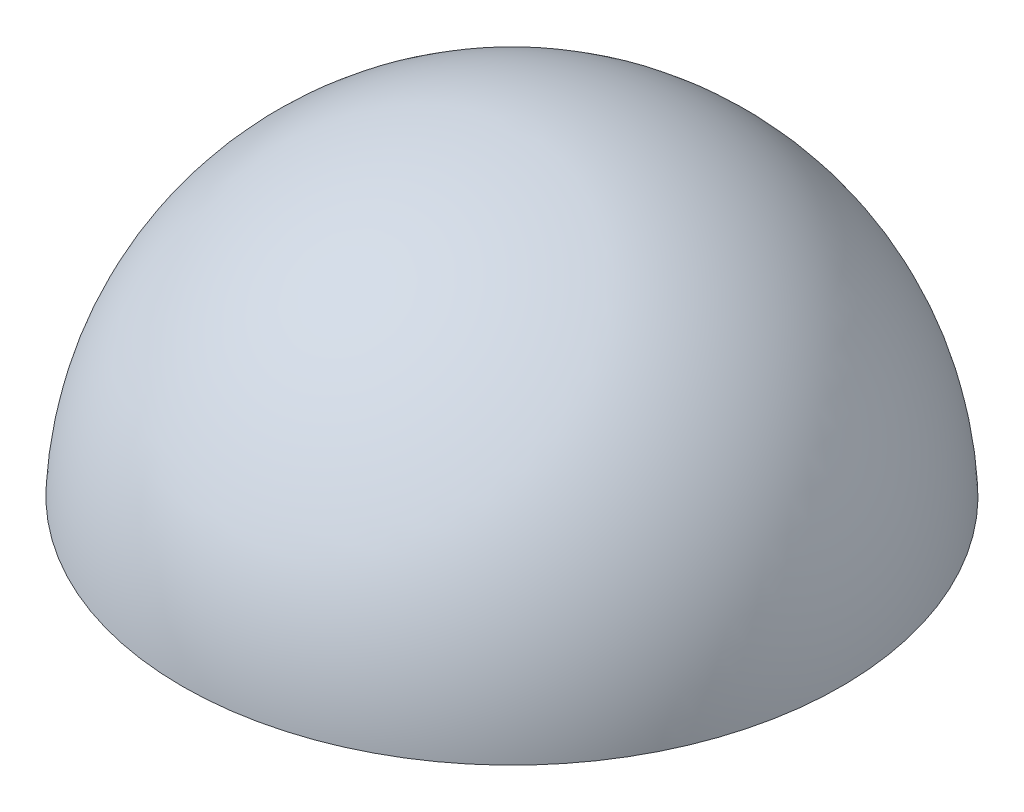
SolidWorks part; units mm, degrees
ref_plane "Front Plane" through (0, 0, 0) normal (0, 0, 1) x (1, 0, 0)
ref_plane "Top Plane" through (0, 0, 0) normal (0, 1, 0) x (1, 0, 0)
ref_plane "Right Plane" through (0, 0, 0) normal (1, 0, 0) x (0, 0, -1)
sketch "Sketch1" plane through (0, 0, 0) normal (0, 1, 0) x (1, 0, 0)
  line L0 (0, -44.45) -> (0, 44.45)
  arc A0 (0, 44.45) -> (0, -44.45) centre (0, 0) ccw
  arc A1 (0, 42.45) -> (0, -42.45) centre (0, 0) ccw
  circle A3 centre (0, 0) radius 44.45 construction
  circle A4 centre (0, 0) radius 42.45 construction
  point P1 (42.45, 0)
  point P6 (42.5077, 12.9959)
  dimension "D1" = 88.9
  dimension "D2" = 2
revolve "Revolve1" add sketch "Sketch1" angle 180 about L0 region at (-43.4561, 0, 0)
sketch "Sketch2" plane through (0, 0, 0) normal (0, 1, 0) x (1, 0, 0)
  circle A0 centre (0, 0) radius 44.45
extrude "Cut-Extrude1" cut sketch "Sketch2" along normal blind 2
sketch "30deg" plane through (0, 0, 0) normal (1, 0, 0) x (0, 0, -1)
  line L0 (0, 0) -> (38.4948, 22.225) construction
  line L1 (0, 0) -> (44.45, 0) construction
  line L7 (0, 0) -> (22.225, 38.4948) construction
  line L8 (0, 0) -> (44.45, 0) construction
  line L10 (0, 0) -> (38.4948, 22.225) construction
  line L25 (0, 0) -> (0, 49000) construction
  dimension "D2" = 3
  dimension "D3" = 30
  dimension "D1" = 44.45
sketch "Sketch4" plane through (0, 0, 0) normal (0, 1, 0) x (1, 0, 0)
  line L0 (0, 0) -> (0, 43.45)
  line L1 (0.5, 44.45) -> (-0.5, 44.45)
  line L2 (-0.5, 43.45) -> (0.5, 43.45)
  line L3 (-0.5, 43.45) -> (-0.5, 44.45)
  line L4 (0.5, 43.45) -> (0.5, 44.45)
  line L5 (0, 0) -> (21.725, 37.6288)
  line L6 (21.292, 37.8788) -> (21.792, 38.7448)
  line L7 (21.292, 37.8788) -> (22.158, 37.3788)
  line L8 (22.158, 37.3788) -> (22.658, 38.2448)
  line L9 (22.658, 38.2448) -> (21.792, 38.7448)
  line L10 (0, 0) -> (37.6288, 21.725)
  line L11 (37.3788, 22.158) -> (38.2448, 22.658)
  line L12 (37.3788, 22.158) -> (37.8788, 21.292)
  line L13 (37.8788, 21.292) -> (38.7448, 21.792)
  line L14 (38.7448, 21.792) -> (38.2448, 22.658)
  line L15 (0, 0) -> (43.45, 0)
  line L16 (43.45, 0.5) -> (44.45, 0.5)
  line L17 (43.45, 0.5) -> (43.45, -0.5)
  line L18 (43.45, -0.5) -> (44.45, -0.5)
  line L19 (44.45, -0.5) -> (44.45, 0.5)
  line L20 (0, 0) -> (37.6288, -21.725)
  line L21 (37.8788, -21.292) -> (38.7448, -21.792)
  line L22 (37.8788, -21.292) -> (37.3788, -22.158)
  line L23 (37.3788, -22.158) -> (38.2448, -22.658)
  line L24 (38.2448, -22.658) -> (38.7448, -21.792)
  line L25 (0, 0) -> (21.725, -37.6288)
  line L26 (22.158, -37.3788) -> (22.658, -38.2448)
  line L27 (22.158, -37.3788) -> (21.292, -37.8788)
  line L28 (21.292, -37.8788) -> (21.792, -38.7448)
  line L29 (21.792, -38.7448) -> (22.658, -38.2448)
  line L30 (0, 0) -> (0, -43.45)
  line L31 (0.5, -43.45) -> (0.5, -44.45)
  line L32 (0.5, -43.45) -> (-0.5, -43.45)
  line L33 (-0.5, -43.45) -> (-0.5, -44.45)
  line L34 (-0.5, -44.45) -> (0.5, -44.45)
  line L35 (0, 0) -> (-21.725, -37.6288)
  line L36 (-21.292, -37.8788) -> (-21.792, -38.7448)
  line L37 (-21.292, -37.8788) -> (-22.158, -37.3788)
  line L38 (-22.158, -37.3788) -> (-22.658, -38.2448)
  line L39 (-22.658, -38.2448) -> (-21.792, -38.7448)
  line L40 (0, 0) -> (-37.6288, -21.725)
  line L41 (-37.3788, -22.158) -> (-38.2448, -22.658)
  line L42 (-37.3788, -22.158) -> (-37.8788, -21.292)
  line L43 (-37.8788, -21.292) -> (-38.7448, -21.792)
  line L44 (-38.7448, -21.792) -> (-38.2448, -22.658)
  line L45 (0, 0) -> (-43.45, 0)
  line L46 (-43.45, -0.5) -> (-44.45, -0.5)
  line L47 (-43.45, -0.5) -> (-43.45, 0.5)
  line L48 (-43.45, 0.5) -> (-44.45, 0.5)
  line L49 (-44.45, 0.5) -> (-44.45, -0.5)
  line L50 (0, 0) -> (-37.6288, 21.725)
  line L51 (-37.8788, 21.292) -> (-38.7448, 21.792)
  line L52 (-37.8788, 21.292) -> (-37.3788, 22.158)
  line L53 (-37.3788, 22.158) -> (-38.2448, 22.658)
  line L54 (-38.2448, 22.658) -> (-38.7448, 21.792)
  line L55 (0, 0) -> (-21.725, 37.6288)
  line L56 (-22.158, 37.3788) -> (-22.658, 38.2448)
  line L57 (-22.158, 37.3788) -> (-21.292, 37.8788)
  line L58 (-21.292, 37.8788) -> (-21.792, 38.7448)
  line L59 (-21.792, 38.7448) -> (-22.658, 38.2448)
  line L60 (0, 0) -> (0, 43.45) construction
  line L61 (0, 0) -> (21.725, 37.6288) construction
  circle A0 centre (0, 0) radius 44.45 construction
  point P7 (0, 44.45)
  point P10 (0, 43.45)
  dimension "D1" = 88.9
  dimension "D2" = 1
  dimension "D3" = 1
  dimension "D5" = 30
  dimension "D4" = 12
ref_plane "Plane1" through (0, 44.45, 0) normal (0, 1, 0) x (1, 0, 0)
sketch "Sketch5" plane through (0, 44.45, 0) normal (0, 1, 0) x (1, 0, 0)
  circle A0 centre (0, 0) radius 0.5
  dimension "D1" = 1
sketch "Sketch6" plane through (0, 0, 0) normal (0, 0, 1) x (1, 0, 0)
  line L0 (44.45, 0) -> (-44.45, 0) construction
  line L1 (-43.45, 0) -> (-44.45, 0) construction
  arc A0 (-44.45, 0) -> (0, 44.45) centre (0, 0) cw
ref_axis "Axis1" through (0, 117.8347, 0) along (0, -1, 0)
sketch "Sketch7" plane through (0, 44.45, 0) normal (0, 1, 0) x (1, 0, 0)
  line L0 (0, 0) -> (0, 88.8986) construction
  line L4 (-0.5, 38.9916) -> (-0.5, 88.8986)
  line L5 (0.5, 38.9916) -> (0.5, 88.8986)
  line L7 (-0.5, 22.7195) -> (-0.5, 37.9915)
  line L9 (0.5, 22.7195) -> (0.5, 37.9915)
  line L10 (0, 0) -> (44.4493, 76.9884) construction
  line L11 (19.0628, 34.0177) -> (44.0163, 77.2384)
  line L12 (19.9288, 33.5177) -> (44.8823, 76.7384)
  line L13 (10.9267, 19.9257) -> (18.5628, 33.1516)
  line L14 (11.7928, 19.4257) -> (19.4288, 32.6516)
  line L17 (0, 0) -> (76.9884, 44.4493) construction
  line L18 (33.5177, 19.9288) -> (76.7384, 44.8823)
  line L19 (34.0177, 19.0628) -> (77.2384, 44.0163)
  line L20 (19.4257, 11.7928) -> (32.6516, 19.4288)
  line L21 (19.9257, 10.9267) -> (33.1516, 18.5628)
  line L24 (0, 0) -> (88.8986, 0) construction
  line L25 (38.9916, 0.5) -> (88.8986, 0.5)
  line L26 (38.9916, -0.5) -> (88.8986, -0.5)
  line L27 (22.7195, 0.5) -> (37.9915, 0.5)
  line L28 (22.7195, -0.5) -> (37.9915, -0.5)
  line L31 (0, 0) -> (76.9884, -44.4493) construction
  line L32 (34.0177, -19.0628) -> (77.2384, -44.0163)
  line L33 (33.5177, -19.9288) -> (76.7384, -44.8823)
  line L34 (19.9257, -10.9267) -> (33.1516, -18.5628)
  line L35 (19.4257, -11.7928) -> (32.6516, -19.4288)
  line L38 (0, 0) -> (44.4493, -76.9884) construction
  line L39 (19.9288, -33.5177) -> (44.8823, -76.7384)
  line L40 (19.0628, -34.0177) -> (44.0163, -77.2384)
  line L41 (11.7928, -19.4257) -> (19.4288, -32.6516)
  line L42 (10.9267, -19.9257) -> (18.5628, -33.1516)
  line L45 (0, 0) -> (0, -88.8986) construction
  line L46 (0.5, -38.9916) -> (0.5, -88.8986)
  line L47 (-0.5, -38.9916) -> (-0.5, -88.8986)
  line L48 (0.5, -22.7195) -> (0.5, -37.9915)
  line L49 (-0.5, -22.7195) -> (-0.5, -37.9915)
  line L52 (0, 0) -> (-44.4493, -76.9884) construction
  line L53 (-19.0628, -34.0177) -> (-44.0163, -77.2384)
  line L54 (-19.9288, -33.5177) -> (-44.8823, -76.7384)
  line L55 (-10.9267, -19.9257) -> (-18.5628, -33.1516)
  line L56 (-11.7928, -19.4257) -> (-19.4288, -32.6516)
  line L59 (0, 0) -> (-76.9884, -44.4493) construction
  line L60 (-33.5177, -19.9288) -> (-76.7384, -44.8823)
  line L61 (-34.0177, -19.0628) -> (-77.2384, -44.0163)
  line L62 (-19.4257, -11.7928) -> (-32.6516, -19.4288)
  line L63 (-19.9257, -10.9267) -> (-33.1516, -18.5628)
  line L66 (0, 0) -> (-88.8986, 0) construction
  line L67 (-38.9916, -0.5) -> (-88.8986, -0.5)
  line L68 (-38.9916, 0.5) -> (-88.8986, 0.5)
  line L69 (-22.7195, -0.5) -> (-37.9915, -0.5)
  line L70 (-22.7195, 0.5) -> (-37.9915, 0.5)
  line L73 (0, 0) -> (-76.9884, 44.4493) construction
  line L74 (-34.0177, 19.0628) -> (-77.2384, 44.0163)
  line L75 (-33.5177, 19.9288) -> (-76.7384, 44.8823)
  line L76 (-19.9257, 10.9267) -> (-33.1516, 18.5628)
  line L77 (-19.4257, 11.7928) -> (-32.6516, 19.4288)
  line L80 (0, 0) -> (-44.4493, 76.9884) construction
  line L81 (-19.9288, 33.5177) -> (-44.8823, 76.7384)
  line L82 (-19.0628, 34.0177) -> (-44.0163, 77.2384)
  line L83 (-11.7928, 19.4257) -> (-19.4288, 32.6516)
  line L84 (-10.9267, 19.9257) -> (-18.5628, 33.1516)
  line L87 (0, 0) -> (0.5, 0) construction
  line L89 (-0.5, 1.866) -> (-0.5, 21.7192)
  line L90 (-0.5, 1.866) -> (-10.4266, 19.0594)
  line L91 (0.5, 1.866) -> (10.4266, 19.0594)
  line L92 (0.5, 1.866) -> (0.5, 21.7192)
  line L93 (1.366, 1.366) -> (18.5594, 11.2926)
  line L94 (1.366, 1.366) -> (11.2926, 18.5594)
  line L95 (1.866, 0.5) -> (21.7192, 0.5)
  line L96 (1.866, 0.5) -> (19.0594, 10.4266)
  line L97 (1.866, -0.5) -> (19.0594, -10.4266)
  line L98 (1.866, -0.5) -> (21.7192, -0.5)
  line L99 (1.366, -1.366) -> (11.2926, -18.5594)
  line L100 (1.366, -1.366) -> (18.5594, -11.2926)
  line L101 (0.5, -1.866) -> (0.5, -21.7192)
  line L102 (0.5, -1.866) -> (10.4266, -19.0594)
  line L103 (-0.5, -1.866) -> (-10.4266, -19.0594)
  line L104 (-0.5, -1.866) -> (-0.5, -21.7192)
  line L105 (-1.366, -1.366) -> (-11.2926, -18.5594)
  line L106 (-1.366, -1.366) -> (-18.5594, -11.2926)
  line L107 (-1.866, -0.5) -> (-21.7192, -0.5)
  line L108 (-1.866, -0.5) -> (-19.0594, -10.4266)
  line L109 (-1.866, 0.5) -> (-19.0594, 10.4266)
  line L110 (-1.866, 0.5) -> (-21.7192, 0.5)
  line L111 (-1.366, 1.366) -> (-11.2926, 18.5594)
  line L112 (-1.366, 1.366) -> (-18.5594, 11.2926)
  circle A0 centre (0, 0) radius 22.225 construction
  circle A1 centre (0, 0) radius 38.4948 construction
  arc A2 (-0.5, 38.9916) -> (-19.0628, 34.0177) centre (0, 0) ccw
  arc A3 (-0.5, 22.7195) -> (-10.9267, 19.9257) centre (0, 0) ccw
  arc A4 (-0.5, 37.9915) -> (-18.5628, 33.1516) centre (0, 0) ccw
  arc A5 (-0.5, 21.7192) -> (-10.4266, 19.0594) centre (0, 0) ccw
  arc A6 (0.5, 88.8986) -> (-0.5, 88.8986) centre (0, 0) ccw
  circle A9 centre (0, 0) radius 88.9 construction
  circle A10 centre (0, 0) radius 38.9948 construction
  circle A11 centre (0, 0) radius 37.9948 construction
  circle A13 centre (0, 0) radius 21.725 construction
  circle A14 centre (0, 0) radius 22.725 construction
  arc A15 (44.8823, 76.7384) -> (44.0163, 77.2384) centre (0, 0) ccw
  arc A16 (77.2384, 44.0163) -> (76.7384, 44.8823) centre (0, 0) ccw
  arc A17 (88.8986, -0.5) -> (88.8986, 0.5) centre (0, 0) ccw
  arc A18 (76.7384, -44.8823) -> (77.2384, -44.0163) centre (0, 0) ccw
  arc A19 (44.0163, -77.2384) -> (44.8823, -76.7384) centre (0, 0) ccw
  arc A20 (-0.5, -88.8986) -> (0.5, -88.8986) centre (0, 0) ccw
  arc A21 (-44.8823, -76.7384) -> (-44.0163, -77.2384) centre (0, 0) ccw
  arc A22 (-77.2384, -44.0163) -> (-76.7384, -44.8823) centre (0, 0) ccw
  arc A23 (-88.8986, 0.5) -> (-88.8986, -0.5) centre (0, 0) ccw
  arc A24 (-76.7384, 44.8823) -> (-77.2384, 44.0163) centre (0, 0) ccw
  arc A25 (-44.0163, 77.2384) -> (-44.8823, 76.7384) centre (0, 0) ccw
  arc A26 (-34.0177, 19.0628) -> (-38.9916, 0.5) centre (0, 0) ccw
  arc A27 (-33.1516, 18.5628) -> (-37.9915, 0.5) centre (0, 0) ccw
  arc A28 (-19.9288, 33.5177) -> (-33.5177, 19.9288) centre (0, 0) ccw
  arc A29 (-19.4288, 32.6516) -> (-32.6516, 19.4288) centre (0, 0) ccw
  arc A30 (19.0628, 34.0177) -> (0.5, 38.9916) centre (0, 0) ccw
  arc A31 (18.5628, 33.1516) -> (0.5, 37.9915) centre (0, 0) ccw
  arc A32 (32.6516, 19.4288) -> (19.4288, 32.6516) centre (0, 0) ccw
  arc A33 (33.5177, 19.9288) -> (19.9288, 33.5177) centre (0, 0) ccw
  arc A34 (37.9915, 0.5) -> (33.1516, 18.5628) centre (0, 0) ccw
  arc A35 (38.9916, 0.5) -> (34.0177, 19.0628) centre (0, 0) ccw
  arc A36 (33.1516, -18.5628) -> (37.9915, -0.5) centre (0, 0) ccw
  arc A37 (34.0177, -19.0628) -> (38.9916, -0.5) centre (0, 0) ccw
  arc A38 (19.4288, -32.6516) -> (32.6516, -19.4288) centre (0, 0) ccw
  arc A39 (19.9288, -33.5177) -> (33.5177, -19.9288) centre (0, 0) ccw
  arc A40 (0.5, -37.9915) -> (18.5628, -33.1516) centre (0, 0) ccw
  arc A41 (0.5, -38.9916) -> (19.0628, -34.0177) centre (0, 0) ccw
  arc A42 (-18.5628, -33.1516) -> (-0.5, -37.9915) centre (0, 0) ccw
  arc A43 (-19.0628, -34.0177) -> (-0.5, -38.9916) centre (0, 0) ccw
  arc A44 (-33.5177, -19.9288) -> (-19.9288, -33.5177) centre (0, 0) ccw
  arc A45 (-32.6516, -19.4288) -> (-19.4288, -32.6516) centre (0, 0) ccw
  arc A46 (-38.9916, -0.5) -> (-34.0177, -19.0628) centre (0, 0) ccw
  arc A47 (-37.9915, -0.5) -> (-33.1516, -18.5628) centre (0, 0) ccw
  arc A48 (-11.7928, 19.4257) -> (-19.4257, 11.7928) centre (0, 0) ccw
  arc A49 (-11.2926, 18.5594) -> (-18.5594, 11.2926) centre (0, 0) ccw
  arc A50 (-19.9257, 10.9267) -> (-22.7195, 0.5) centre (0, 0) ccw
  arc A51 (-19.0594, 10.4266) -> (-21.7192, 0.5) centre (0, 0) ccw
  arc A52 (-21.7192, -0.5) -> (-19.0594, -10.4266) centre (0, 0) ccw
  arc A53 (-22.7195, -0.5) -> (-19.9257, -10.9267) centre (0, 0) ccw
  arc A54 (10.4266, 19.0594) -> (0.5, 21.7192) centre (0, 0) ccw
  arc A55 (10.9267, 19.9257) -> (0.5, 22.7195) centre (0, 0) ccw
  arc A56 (18.5594, 11.2926) -> (11.2926, 18.5594) centre (0, 0) ccw
  arc A57 (19.4257, 11.7928) -> (11.7928, 19.4257) centre (0, 0) ccw
  arc A58 (21.7192, 0.5) -> (19.0594, 10.4266) centre (0, 0) ccw
  arc A59 (22.7195, 0.5) -> (19.9257, 10.9267) centre (0, 0) ccw
  arc A60 (19.9257, -10.9267) -> (22.7195, -0.5) centre (0, 0) ccw
  arc A61 (19.0594, -10.4266) -> (21.7192, -0.5) centre (0, 0) ccw
  arc A62 (11.2926, -18.5594) -> (18.5594, -11.2926) centre (0, 0) ccw
  arc A63 (11.7928, -19.4257) -> (19.4257, -11.7928) centre (0, 0) ccw
  arc A64 (0.5, -22.7195) -> (10.9267, -19.9257) centre (0, 0) ccw
  arc A65 (0.5, -21.7192) -> (10.4266, -19.0594) centre (0, 0) ccw
  arc A66 (-10.4266, -19.0594) -> (-0.5, -21.7192) centre (0, 0) ccw
  arc A67 (-10.9267, -19.9257) -> (-0.5, -22.7195) centre (0, 0) ccw
  arc A68 (-19.4257, -11.7928) -> (-11.7928, -19.4257) centre (0, 0) ccw
  arc A69 (-18.5594, -11.2926) -> (-11.2926, -18.5594) centre (0, 0) ccw
  point P11 (21.725, 0)
  point P13 (22.725, 0)
  point P17 (0.5, 0)
  point P19 (-0.5, 0)
  point P27 (38.9948, 0)
  point P30 (37.9948, 0)
  point P114 (-1.366, 1.366)
  dimension "D5" = 177.8
  dimension "D1" = 0.5
  dimension "D2" = 0.5
  dimension "D6" = 12
sketch "Sketch9" plane through (0, 44.45, 0) normal (0, 1, 0) x (1, 0, 0)
  line L0 (0, 0) -> (0, -88.9)
  circle A0 centre (0, 0) radius 22.225
  circle A1 centre (0, 0) radius 38.4948
  circle A2 centre (0, 0) radius 88.9
  circle A3 centre (0, 0) radius 38.4948 construction
  circle A4 centre (0, 0) radius 22.225 construction
  dimension "D1" = 177.8
sketch "Sketch10" plane through (0, 44.45, 0) normal (0, 1, 0) x (1, 0, 0)
  line L0 (88.9, 0) -> (-88.9, 0) construction
  line L1 (0, 88.9) -> (0, -88.9) construction
  line L2 (-29.64, 88.9) -> (-29.64, -88.9) construction
  line L3 (-59.28, 88.9) -> (-59.28, -88.9) construction
  line L4 (-88.92, 88.9) -> (-88.92, -88.9) construction
  line L5 (29.64, 88.9) -> (29.64, -88.9) construction
  line L6 (59.28, 88.9) -> (59.28, -88.9) construction
  line L7 (88.92, 88.9) -> (88.92, -88.9) construction
  line L8 (-89.42, 88.9) -> (-89.42, -88.9)
  line L9 (-59.78, 88.9) -> (-59.78, 0.5)
  line L10 (-30.14, 88.9) -> (-30.14, 0.5)
  line L11 (-0.5, 88.9) -> (-0.5, 0.5)
  line L12 (29.14, 88.9) -> (29.14, 0.5)
  line L13 (58.78, 88.9) -> (58.78, 0.5)
  line L14 (88.42, 88.9) -> (88.42, 0.5)
  line L15 (-88.42, 88.9) -> (-88.42, 0.5)
  line L16 (-58.78, 88.9) -> (-58.78, 0.5)
  line L17 (-29.14, 88.9) -> (-29.14, 0.5)
  line L18 (0.5, 88.9) -> (0.5, 0.5)
  line L19 (30.14, 88.9) -> (30.14, 0.5)
  line L20 (59.78, 88.9) -> (59.78, 0.5)
  line L21 (89.42, 88.9) -> (89.42, -88.9)
  line L22 (88.42, 0.5) -> (59.78, 0.5)
  line L23 (88.42, -0.5) -> (59.78, -0.5)
  line L24 (-88.42, -0.5) -> (-88.42, -88.9)
  line L25 (88.9, 0.5) -> (-88.9, 0.5) construction
  line L26 (88.9, -0.5) -> (-88.9, -0.5) construction
  line L27 (-59.78, 0.5) -> (-88.42, 0.5)
  line L28 (-88.42, 88.9) -> (-88.42, -88.9) construction
  line L29 (-59.78, -0.5) -> (-88.42, -0.5)
  line L30 (-59.78, -0.5) -> (-59.78, -88.9)
  line L31 (-58.78, -0.5) -> (-58.78, -88.9)
  line L32 (-59.78, 88.9) -> (-59.78, -88.9) construction
  line L33 (-30.14, -0.5) -> (-30.14, -88.9)
  line L34 (-58.78, 88.9) -> (-58.78, -88.9) construction
  line L35 (-30.14, 88.9) -> (-30.14, -88.9) construction
  line L36 (-29.14, -0.5) -> (-29.14, -88.9)
  line L37 (-29.14, 88.9) -> (-29.14, -88.9) construction
  line L38 (-0.5, -0.5) -> (-0.5, -88.9)
  line L39 (-0.5, 88.9) -> (-0.5, -88.9) construction
  line L40 (0.5, -0.5) -> (0.5, -88.9)
  line L41 (0.5, 88.9) -> (0.5, -88.9) construction
  line L42 (29.14, -0.5) -> (29.14, -88.9)
  line L43 (29.14, 88.9) -> (29.14, -88.9) construction
  line L44 (30.14, -0.5) -> (30.14, -88.9)
  line L45 (30.14, 88.9) -> (30.14, -88.9) construction
  line L46 (58.78, -0.5) -> (58.78, -88.9)
  line L47 (58.78, 88.9) -> (58.78, -88.9) construction
  line L48 (59.78, -0.5) -> (59.78, -88.9)
  line L49 (59.78, 88.9) -> (59.78, -88.9) construction
  line L50 (88.42, -0.5) -> (88.42, -88.9)
  line L51 (88.42, 88.9) -> (88.42, -88.9) construction
  line L52 (58.78, 0.5) -> (30.14, 0.5)
  line L53 (58.78, -0.5) -> (30.14, -0.5)
  line L54 (-30.14, 0.5) -> (-58.78, 0.5)
  line L55 (-30.14, -0.5) -> (-58.78, -0.5)
  line L56 (-0.5, 0.5) -> (-29.14, 0.5)
  line L57 (-0.5, -0.5) -> (-29.14, -0.5)
  line L58 (29.14, 0.5) -> (0.5, 0.5)
  line L59 (29.14, -0.5) -> (0.5, -0.5)
  arc A0 (-89.42, 88.9) -> (-88.42, 88.9) centre (-88.92, 88.9) cw
  arc A1 (-89.42, -88.9) -> (-88.42, -88.9) centre (-88.92, -88.9) ccw
  arc A2 (-59.78, 88.9) -> (-58.78, 88.9) centre (-59.28, 88.9) cw
  arc A3 (-59.78, -88.9) -> (-58.78, -88.9) centre (-59.28, -88.9) ccw
  arc A4 (-30.14, 88.9) -> (-29.14, 88.9) centre (-29.64, 88.9) cw
  arc A5 (-30.14, -88.9) -> (-29.14, -88.9) centre (-29.64, -88.9) ccw
  arc A6 (-0.5, 88.9) -> (0.5, 88.9) centre (0, 88.9) cw
  arc A7 (-0.5, -88.9) -> (0.5, -88.9) centre (0, -88.9) ccw
  arc A8 (29.14, 88.9) -> (30.14, 88.9) centre (29.64, 88.9) cw
  arc A9 (29.14, -88.9) -> (30.14, -88.9) centre (29.64, -88.9) ccw
  arc A10 (58.78, 88.9) -> (59.78, 88.9) centre (59.28, 88.9) cw
  arc A11 (58.78, -88.9) -> (59.78, -88.9) centre (59.28, -88.9) ccw
  arc A12 (88.42, 88.9) -> (89.42, 88.9) centre (88.92, 88.9) cw
  arc A13 (88.42, -88.9) -> (89.42, -88.9) centre (88.92, -88.9) ccw
  arc A15 (-88.9, 0.5) -> (-88.92, 0.4996) centre (-88.9, 0) ccw
  arc A16 (-88.92, -0.4996) -> (-88.9, -0.5) centre (-88.9, 0) ccw
  point P4 (0, 0)
  point P8 (0, 0)
  dimension "D1" = 177.8
  dimension "D3" = 0.5
  dimension "D4" = 0.5
  dimension "D5" = 0.5
  dimension "D6" = 0.5
  dimension "D2" = 4
sketch "Sketch13" plane through (0, 44.45, 0) normal (0, 1, 0) x (1, 0, 0)
  line L0 (0, -11.5265) -> (0, 11.5265) construction
  line L1 (-11.5265, 0) -> (11.5265, 0) construction
  line L2 (-11.5265, -0.5) -> (-0.5, -0.5)
  line L3 (-18.1069, 3.2902) -> (-11.5265, 3.2902) construction
  line L4 (-18.1069, 3.2902) -> (-18.1069, -3.2902) construction
  line L5 (-18.1069, -3.2902) -> (-11.5265, -3.2902) construction
  line L6 (-11.5265, 3.2902) -> (-11.5265, -3.2902) construction
  line L7 (-3.2902, 18.1069) -> (3.2902, 18.1069) construction
  line L8 (-3.2902, 18.1069) -> (-3.2902, 11.5265) construction
  line L9 (-3.2902, 11.5265) -> (3.2902, 11.5265) construction
  line L10 (3.2902, 18.1069) -> (3.2902, 11.5265) construction
  line L11 (0.5, -11.5265) -> (0.5, -0.5)
  line L12 (-11.5265, 0.5) -> (-0.5, 0.5)
  line L13 (-0.5, -11.5265) -> (-0.5, -0.5)
  line L14 (-0.5, 0.5) -> (-0.5, 11.5265)
  line L15 (0.5, 0.5) -> (0.5, 11.5265)
  line L16 (-0.5, -11.5265) -> (-0.5, 11.5265) construction
  line L17 (0.5, 0.5) -> (11.5265, 0.5)
  line L18 (0.5, -11.5265) -> (0.5, 11.5265) construction
  line L19 (0.5, -0.5) -> (11.5265, -0.5)
  line L20 (-11.5265, 0.5) -> (11.5265, 0.5) construction
  line L21 (-11.5265, 0.5) -> (-11.5265, -0.5)
  line L22 (-11.5265, -0.5) -> (11.5265, -0.5) construction
  line L23 (11.5265, 0.5) -> (11.5265, -0.5)
  line L24 (-0.5, -11.5265) -> (0.5, -11.5265)
  line L25 (-0.5, 11.5265) -> (0.5, 11.5265)
  line L26 (18.1035, -0.5) -> (29.13, -0.5)
  line L27 (30.13, -11.5265) -> (30.13, -0.5)
  line L28 (18.1035, 0.5) -> (29.13, 0.5)
  line L29 (29.13, -11.5265) -> (29.13, -0.5)
  line L30 (29.13, 0.5) -> (29.13, 11.5265)
  line L31 (30.13, 0.5) -> (30.13, 11.5265)
  line L32 (30.13, 0.5) -> (41.1565, 0.5)
  line L33 (30.13, -0.5) -> (41.1565, -0.5)
  line L34 (18.1035, 0.5) -> (18.1035, -0.5)
  line L35 (41.1565, 0.5) -> (41.1565, -0.5)
  line L36 (29.13, -11.5265) -> (30.13, -11.5265)
  line L37 (29.13, 11.5265) -> (30.13, 11.5265)
  line L38 (29.63, -11.5265) -> (29.63, 11.5265) construction
  line L39 (18.1035, 0) -> (41.1565, 0) construction
  line L40 (11.5231, 3.2902) -> (18.1035, 3.2902) construction
  line L41 (11.5231, 3.2902) -> (11.5231, -3.2902) construction
  line L42 (11.5231, -3.2902) -> (18.1035, -3.2902) construction
  line L43 (18.1035, 3.2902) -> (18.1035, -3.2902) construction
  line L44 (26.3398, 18.1069) -> (32.9202, 18.1069) construction
  line L45 (26.3398, 18.1069) -> (26.3398, 11.5265) construction
  line L46 (26.3398, 11.5265) -> (32.9202, 11.5265) construction
  line L47 (32.9202, 18.1069) -> (32.9202, 11.5265) construction
  line L48 (47.7335, -0.5) -> (58.76, -0.5)
  line L49 (59.76, -11.5265) -> (59.76, -0.5)
  line L50 (47.7335, 0.5) -> (58.76, 0.5)
  line L51 (58.76, -11.5265) -> (58.76, -0.5)
  line L52 (58.76, 0.5) -> (58.76, 11.5265)
  line L53 (59.76, 0.5) -> (59.76, 11.5265)
  line L54 (59.76, 0.5) -> (70.7865, 0.5)
  line L55 (59.76, -0.5) -> (70.7865, -0.5)
  line L56 (47.7335, 0.5) -> (47.7335, -0.5)
  line L57 (70.7865, 0.5) -> (70.7865, -0.5)
  line L58 (58.76, -11.5265) -> (59.76, -11.5265)
  line L59 (58.76, 11.5265) -> (59.76, 11.5265)
  line L60 (59.26, -11.5265) -> (59.26, 11.5265) construction
  line L61 (47.7335, 0) -> (70.7865, 0) construction
  line L62 (41.1531, 3.2902) -> (47.7335, 3.2902) construction
  line L63 (41.1531, 3.2902) -> (41.1531, -3.2902) construction
  line L64 (41.1531, -3.2902) -> (47.7335, -3.2902) construction
  line L65 (47.7335, 3.2902) -> (47.7335, -3.2902) construction
  line L66 (55.9698, 18.1069) -> (62.5502, 18.1069) construction
  line L67 (55.9698, 18.1069) -> (55.9698, 11.5265) construction
  line L68 (55.9698, 11.5265) -> (62.5502, 11.5265) construction
  line L69 (62.5502, 18.1069) -> (62.5502, 11.5265) construction
  line L70 (-11.5265, 29.13) -> (-0.5, 29.13)
  line L71 (0.5, 18.1035) -> (0.5, 29.13)
  line L72 (-11.5265, 30.13) -> (-0.5, 30.13)
  line L73 (-0.5, 18.1035) -> (-0.5, 29.13)
  line L74 (-0.5, 30.13) -> (-0.5, 41.1565)
  line L75 (0.5, 30.13) -> (0.5, 41.1565)
  line L76 (0.5, 30.13) -> (11.5265, 30.13)
  line L77 (0.5, 29.13) -> (11.5265, 29.13)
  line L78 (-11.5265, 30.13) -> (-11.5265, 29.13)
  line L79 (11.5265, 30.13) -> (11.5265, 29.13)
  line L80 (-0.5, 18.1035) -> (0.5, 18.1035)
  line L81 (-0.5, 41.1565) -> (0.5, 41.1565)
  line L82 (18.1035, 29.13) -> (29.13, 29.13)
  line L83 (30.13, 18.1035) -> (30.13, 29.13)
  line L84 (18.1035, 30.13) -> (29.13, 30.13)
  line L85 (29.13, 18.1035) -> (29.13, 29.13)
  line L86 (29.13, 30.13) -> (29.13, 41.1565)
  line L87 (30.13, 30.13) -> (30.13, 41.1565)
  line L88 (30.13, 30.13) -> (41.1565, 30.13)
  line L89 (30.13, 29.13) -> (41.1565, 29.13)
  line L90 (18.1035, 30.13) -> (18.1035, 29.13)
  line L91 (41.1565, 30.13) -> (41.1565, 29.13)
  line L92 (29.13, 18.1035) -> (30.13, 18.1035)
  line L93 (29.13, 41.1565) -> (30.13, 41.1565)
  line L94 (47.7335, 29.13) -> (58.76, 29.13)
  line L95 (59.76, 18.1035) -> (59.76, 29.13)
  line L96 (47.7335, 30.13) -> (58.76, 30.13)
  line L97 (58.76, 18.1035) -> (58.76, 29.13)
  line L98 (58.76, 30.13) -> (58.76, 41.1565)
  line L99 (59.76, 30.13) -> (59.76, 41.1565)
  line L100 (59.76, 30.13) -> (70.7865, 30.13)
  line L101 (59.76, 29.13) -> (70.7865, 29.13)
  line L102 (47.7335, 30.13) -> (47.7335, 29.13)
  line L103 (70.7865, 30.13) -> (70.7865, 29.13)
  line L104 (58.76, 18.1035) -> (59.76, 18.1035)
  line L105 (58.76, 41.1565) -> (59.76, 41.1565)
  line L106 (0, 18.1035) -> (0, 41.1565) construction
  line L107 (-11.5265, 29.63) -> (11.5265, 29.63) construction
  line L108 (-18.1069, 32.9202) -> (-11.5265, 32.9202) construction
  line L109 (-18.1069, 32.9202) -> (-18.1069, 26.3398) construction
  line L110 (-18.1069, 26.3398) -> (-11.5265, 26.3398) construction
  line L111 (-11.5265, 32.9202) -> (-11.5265, 26.3398) construction
  line L112 (-3.2902, 47.7369) -> (3.2902, 47.7369) construction
  line L113 (-3.2902, 47.7369) -> (-3.2902, 41.1565) construction
  line L114 (-3.2902, 41.1565) -> (3.2902, 41.1565) construction
  line L115 (3.2902, 47.7369) -> (3.2902, 41.1565) construction
  line L116 (29.63, 18.1035) -> (29.63, 41.1565) construction
  line L117 (18.1035, 29.63) -> (41.1565, 29.63) construction
  line L118 (11.5231, 32.9202) -> (18.1035, 32.9202) construction
  line L119 (11.5231, 32.9202) -> (11.5231, 26.3398) construction
  line L120 (11.5231, 26.3398) -> (18.1035, 26.3398) construction
  line L121 (18.1035, 32.9202) -> (18.1035, 26.3398) construction
  line L122 (26.3398, 47.7369) -> (32.9202, 47.7369) construction
  line L123 (26.3398, 47.7369) -> (26.3398, 41.1565) construction
  line L124 (26.3398, 41.1565) -> (32.9202, 41.1565) construction
  line L125 (32.9202, 47.7369) -> (32.9202, 41.1565) construction
  line L126 (59.26, 18.1035) -> (59.26, 41.1565) construction
  line L127 (47.7335, 29.63) -> (70.7865, 29.63) construction
  line L128 (41.1531, 32.9202) -> (47.7335, 32.9202) construction
  line L129 (41.1531, 32.9202) -> (41.1531, 26.3398) construction
  line L130 (41.1531, 26.3398) -> (47.7335, 26.3398) construction
  line L131 (47.7335, 32.9202) -> (47.7335, 26.3398) construction
  line L132 (55.9698, 47.7369) -> (62.5502, 47.7369) construction
  line L133 (55.9698, 47.7369) -> (55.9698, 41.1565) construction
  line L134 (55.9698, 41.1565) -> (62.5502, 41.1565) construction
  line L135 (62.5502, 47.7369) -> (62.5502, 41.1565) construction
  line L136 (-11.5265, 58.76) -> (-0.5, 58.76)
  line L137 (0.5, 47.7335) -> (0.5, 58.76)
  line L138 (-11.5265, 59.76) -> (-0.5, 59.76)
  line L139 (-0.5, 47.7335) -> (-0.5, 58.76)
  line L140 (-0.5, 59.76) -> (-0.5, 70.7865)
  line L141 (0.5, 59.76) -> (0.5, 70.7865)
  line L142 (0.5, 59.76) -> (11.5265, 59.76)
  line L143 (0.5, 58.76) -> (11.5265, 58.76)
  line L144 (-11.5265, 59.76) -> (-11.5265, 58.76)
  line L145 (11.5265, 59.76) -> (11.5265, 58.76)
  line L146 (-0.5, 47.7335) -> (0.5, 47.7335)
  line L147 (-0.5, 70.7865) -> (0.5, 70.7865)
  line L148 (18.1035, 58.76) -> (29.13, 58.76)
  line L149 (30.13, 47.7335) -> (30.13, 58.76)
  line L150 (18.1035, 59.76) -> (29.13, 59.76)
  line L151 (29.13, 47.7335) -> (29.13, 58.76)
  line L152 (29.13, 59.76) -> (29.13, 70.7865)
  line L153 (30.13, 59.76) -> (30.13, 70.7865)
  line L154 (30.13, 59.76) -> (41.1565, 59.76)
  line L155 (30.13, 58.76) -> (41.1565, 58.76)
  line L156 (18.1035, 59.76) -> (18.1035, 58.76)
  line L157 (41.1565, 59.76) -> (41.1565, 58.76)
  line L158 (29.13, 47.7335) -> (30.13, 47.7335)
  line L159 (29.13, 70.7865) -> (30.13, 70.7865)
  line L160 (47.7335, 58.76) -> (58.76, 58.76)
  line L161 (59.76, 47.7335) -> (59.76, 58.76)
  line L162 (47.7335, 59.76) -> (58.76, 59.76)
  line L163 (58.76, 47.7335) -> (58.76, 58.76)
  line L164 (58.76, 59.76) -> (58.76, 70.7865)
  line L165 (59.76, 59.76) -> (59.76, 70.7865)
  line L166 (59.76, 59.76) -> (70.7865, 59.76)
  line L167 (59.76, 58.76) -> (70.7865, 58.76)
  line L168 (47.7335, 59.76) -> (47.7335, 58.76)
  line L169 (70.7865, 59.76) -> (70.7865, 58.76)
  line L170 (58.76, 47.7335) -> (59.76, 47.7335)
  line L171 (58.76, 70.7865) -> (59.76, 70.7865)
  line L172 (0, 47.7335) -> (0, 70.7865) construction
  line L173 (-11.5265, 59.26) -> (11.5265, 59.26) construction
  line L174 (-18.1069, 62.5502) -> (-11.5265, 62.5502) construction
  line L175 (-18.1069, 62.5502) -> (-18.1069, 55.9698) construction
  line L176 (-18.1069, 55.9698) -> (-11.5265, 55.9698) construction
  line L177 (-11.5265, 62.5502) -> (-11.5265, 55.9698) construction
  line L178 (-3.2902, 77.3669) -> (3.2902, 77.3669) construction
  line L179 (-3.2902, 77.3669) -> (-3.2902, 70.7865) construction
  line L180 (-3.2902, 70.7865) -> (3.2902, 70.7865) construction
  line L181 (3.2902, 77.3669) -> (3.2902, 70.7865) construction
  line L182 (29.63, 47.7335) -> (29.63, 70.7865) construction
  line L183 (18.1035, 59.26) -> (41.1565, 59.26) construction
  line L184 (11.5231, 62.5502) -> (18.1035, 62.5502) construction
  line L185 (11.5231, 62.5502) -> (11.5231, 55.9698) construction
  line L186 (11.5231, 55.9698) -> (18.1035, 55.9698) construction
  line L187 (18.1035, 62.5502) -> (18.1035, 55.9698) construction
  line L188 (26.3398, 77.3669) -> (32.9202, 77.3669) construction
  line L189 (26.3398, 77.3669) -> (26.3398, 70.7865) construction
  line L190 (26.3398, 70.7865) -> (32.9202, 70.7865) construction
  line L191 (32.9202, 77.3669) -> (32.9202, 70.7865) construction
  line L192 (59.26, 47.7335) -> (59.26, 70.7865) construction
  line L193 (47.7335, 59.26) -> (70.7865, 59.26) construction
  line L194 (41.1531, 62.5502) -> (47.7335, 62.5502) construction
  line L195 (41.1531, 62.5502) -> (41.1531, 55.9698) construction
  line L196 (41.1531, 55.9698) -> (47.7335, 55.9698) construction
  line L197 (47.7335, 62.5502) -> (47.7335, 55.9698) construction
  line L198 (55.9698, 77.3669) -> (62.5502, 77.3669) construction
  line L199 (55.9698, 77.3669) -> (55.9698, 70.7865) construction
  line L200 (55.9698, 70.7865) -> (62.5502, 70.7865) construction
  line L201 (62.5502, 77.3669) -> (62.5502, 70.7865) construction
  circle A0 centre (0, 0) radius 88.9 construction
  point P4 (0, 0)
  point P8 (0, 0)
  point P12 (-11.5265, 0)
  point P35 (29.63, 0)
  point P38 (29.63, 0)
  point P61 (59.26, 0)
  point P64 (59.26, 0)
  point P86 (0, 29.63)
  point P89 (0, 29.63)
  point P112 (29.63, 29.63)
  point P115 (29.63, 29.63)
  point P138 (59.26, 29.63)
  point P141 (59.26, 29.63)
  point P164 (0, 59.26)
  point P167 (0, 59.26)
  point P190 (29.63, 59.26)
  point P193 (29.63, 59.26)
  point P216 (59.26, 59.26)
  point P219 (59.26, 59.26)
  dimension "D1" = 177.8
  dimension "D2" = 29.6333
  dimension "D3" = 0.5
  dimension "D4" = 0.5
  dimension "D5" = 3
  dimension "D6" = 3
sketch "Sketch14" plane through (0, 44.45, 0) normal (0, 1, 0) x (1, 0, 0)
  line L0 (94.2855, -48.3857) -> (94.2855, -57.7964) construction
  line L13 (98.9909, -53.0911) -> (89.5802, -53.0911) construction
  line L14 (98.9909, -52.5911) -> (94.7855, -52.5911)
  line L15 (84.1742, -55.7941) -> (89.5802, -55.7941) construction
  line L16 (84.1742, -55.7941) -> (84.1742, -50.3881) construction
  line L17 (84.1742, -50.3881) -> (89.5802, -50.3881) construction
  line L18 (89.5802, -55.7941) -> (89.5802, -50.3881) construction
  line L19 (98.9909, -37.7711) -> (94.7855, -37.7711)
  line L20 (93.7855, -33.5657) -> (93.7855, -37.7711)
  line L21 (91.5825, -42.9798) -> (96.9885, -42.9798) construction
  line L22 (91.5825, -42.9798) -> (91.5825, -48.3857) construction
  line L23 (91.5825, -48.3857) -> (96.9885, -48.3857) construction
  line L24 (96.9885, -42.9798) -> (96.9885, -48.3857) construction
  line L25 (98.9909, -38.7711) -> (94.7855, -38.7711)
  line L26 (94.7855, -33.5657) -> (94.7855, -37.7711)
  line L27 (93.7855, -48.3857) -> (93.7855, -52.5911)
  line L28 (98.9909, -53.5911) -> (94.7855, -53.5911)
  line L29 (94.7855, -48.3857) -> (94.7855, -52.5911)
  line L30 (98.9909, -52.5911) -> (98.9909, -53.5911)
  line L31 (89.5802, -52.5911) -> (89.5802, -53.5911)
  line L32 (93.7855, -48.3857) -> (94.7855, -48.3857)
  line L33 (93.7855, -57.7964) -> (94.7855, -57.7964)
  line L34 (93.7855, -53.5911) -> (93.7855, -57.7964)
  line L35 (93.7855, -53.5911) -> (89.5802, -53.5911)
  line L36 (93.7855, -48.3857) -> (93.7855, -57.7964) construction
  line L37 (94.7855, -53.5911) -> (94.7855, -57.7964)
  line L38 (98.9909, -53.5911) -> (89.5802, -53.5911) construction
  line L39 (93.7855, -52.5911) -> (89.5802, -52.5911)
  line L40 (94.7855, -48.3857) -> (94.7855, -57.7964) construction
  line L41 (98.9909, -37.7711) -> (98.9909, -38.7711)
  line L42 (98.9909, -52.5911) -> (89.5802, -52.5911) construction
  line L43 (89.5802, -37.7711) -> (89.5802, -38.7711)
  line L44 (93.7855, -33.5657) -> (94.7855, -33.5657)
  line L45 (93.7855, -42.9764) -> (94.7855, -42.9764)
  line L46 (93.7855, -38.7711) -> (93.7855, -42.9764)
  line L47 (93.7855, -38.7711) -> (89.5802, -38.7711)
  line L48 (94.7855, -38.7711) -> (94.7855, -42.9764)
  line L49 (93.7855, -37.7711) -> (89.5802, -37.7711)
  line L50 (94.2855, -33.5657) -> (94.2855, -42.9764) construction
  line L51 (98.9909, -38.2711) -> (89.5802, -38.2711) construction
  line L52 (84.1742, -40.9741) -> (89.5802, -40.9741) construction
  line L53 (84.1742, -40.9741) -> (84.1742, -35.5681) construction
  line L54 (84.1742, -35.5681) -> (89.5802, -35.5681) construction
  line L55 (89.5802, -40.9741) -> (89.5802, -35.5681) construction
  line L56 (91.5825, -28.1598) -> (96.9885, -28.1598) construction
  line L57 (91.5825, -28.1598) -> (91.5825, -33.5657) construction
  line L58 (91.5825, -33.5657) -> (96.9885, -33.5657) construction
  line L59 (96.9885, -28.1598) -> (96.9885, -33.5657) construction
  line L60 (98.9909, -22.9511) -> (94.7855, -22.9511)
  line L61 (93.7855, -18.7457) -> (93.7855, -22.9511)
  line L62 (98.9909, -23.9511) -> (94.7855, -23.9511)
  line L63 (94.7855, -18.7457) -> (94.7855, -22.9511)
  line L64 (98.9909, -22.9511) -> (98.9909, -23.9511)
  line L65 (89.5802, -22.9511) -> (89.5802, -23.9511)
  line L66 (93.7855, -18.7457) -> (94.7855, -18.7457)
  line L67 (93.7855, -28.1564) -> (94.7855, -28.1564)
  line L68 (93.7855, -23.9511) -> (93.7855, -28.1564)
  line L69 (93.7855, -23.9511) -> (89.5802, -23.9511)
  line L70 (94.7855, -23.9511) -> (94.7855, -28.1564)
  line L71 (93.7855, -22.9511) -> (89.5802, -22.9511)
  line L72 (94.2855, -18.7457) -> (94.2855, -28.1564) construction
  line L73 (98.9909, -23.4511) -> (89.5802, -23.4511) construction
  line L74 (84.1742, -26.1541) -> (89.5802, -26.1541) construction
  line L75 (84.1742, -26.1541) -> (84.1742, -20.7481) construction
  line L76 (84.1742, -20.7481) -> (89.5802, -20.7481) construction
  line L77 (89.5802, -26.1541) -> (89.5802, -20.7481) construction
  line L78 (91.5825, -13.3398) -> (96.9885, -13.3398) construction
  line L79 (91.5825, -13.3398) -> (91.5825, -18.7457) construction
  line L80 (91.5825, -18.7457) -> (96.9885, -18.7457) construction
  line L81 (96.9885, -13.3398) -> (96.9885, -18.7457) construction
  line L82 (98.9909, -8.1311) -> (94.7855, -8.1311)
  line L83 (93.7855, -3.9257) -> (93.7855, -8.1311)
  line L84 (98.9909, -9.1311) -> (94.7855, -9.1311)
  line L85 (94.7855, -3.9257) -> (94.7855, -8.1311)
  line L86 (98.9909, -8.1311) -> (98.9909, -9.1311)
  line L87 (89.5802, -8.1311) -> (89.5802, -9.1311)
  line L88 (93.7855, -3.9257) -> (94.7855, -3.9257)
  line L89 (93.7855, -13.3364) -> (94.7855, -13.3364)
  line L90 (93.7855, -9.1311) -> (93.7855, -13.3364)
  line L91 (93.7855, -9.1311) -> (89.5802, -9.1311)
  line L92 (94.7855, -9.1311) -> (94.7855, -13.3364)
  line L93 (93.7855, -8.1311) -> (89.5802, -8.1311)
  line L94 (94.2855, -3.9257) -> (94.2855, -13.3364) construction
  line L95 (98.9909, -8.6311) -> (89.5802, -8.6311) construction
  line L96 (84.1742, -11.3341) -> (89.5802, -11.3341) construction
  line L97 (84.1742, -11.3341) -> (84.1742, -5.9281) construction
  line L98 (84.1742, -5.9281) -> (89.5802, -5.9281) construction
  line L99 (89.5802, -11.3341) -> (89.5802, -5.9281) construction
  line L100 (91.5825, 1.4802) -> (96.9885, 1.4802) construction
  line L101 (91.5825, 1.4802) -> (91.5825, -3.9257) construction
  line L102 (91.5825, -3.9257) -> (96.9885, -3.9257) construction
  line L103 (96.9885, 1.4802) -> (96.9885, -3.9257) construction
  line L104 (98.9909, 6.6889) -> (94.7855, 6.6889)
  line L105 (93.7855, 10.8943) -> (93.7855, 6.6889)
  line L106 (98.9909, 5.6889) -> (94.7855, 5.6889)
  line L107 (94.7855, 10.8943) -> (94.7855, 6.6889)
  line L108 (98.9909, 6.6889) -> (98.9909, 5.6889)
  line L109 (89.5802, 6.6889) -> (89.5802, 5.6889)
  line L110 (93.7855, 10.8943) -> (94.7855, 10.8943)
  line L111 (93.7855, 1.4836) -> (94.7855, 1.4836)
  line L112 (93.7855, 5.6889) -> (93.7855, 1.4836)
  line L113 (93.7855, 5.6889) -> (89.5802, 5.6889)
  line L114 (94.7855, 5.6889) -> (94.7855, 1.4836)
  line L115 (93.7855, 6.6889) -> (89.5802, 6.6889)
  line L116 (94.2855, 10.8943) -> (94.2855, 1.4836) construction
  line L117 (98.9909, 6.1889) -> (89.5802, 6.1889) construction
  line L118 (84.1742, 3.4859) -> (89.5802, 3.4859) construction
  line L119 (84.1742, 3.4859) -> (84.1742, 8.8919) construction
  line L120 (84.1742, 8.8919) -> (89.5802, 8.8919) construction
  line L121 (89.5802, 3.4859) -> (89.5802, 8.8919) construction
  line L122 (91.5825, 16.3002) -> (96.9885, 16.3002) construction
  line L123 (91.5825, 16.3002) -> (91.5825, 10.8943) construction
  line L124 (91.5825, 10.8943) -> (96.9885, 10.8943) construction
  line L125 (96.9885, 16.3002) -> (96.9885, 10.8943) construction
  line L126 (98.9909, 21.5089) -> (94.7855, 21.5089)
  line L127 (93.7855, 25.7143) -> (93.7855, 21.5089)
  line L128 (98.9909, 20.5089) -> (94.7855, 20.5089)
  line L129 (94.7855, 25.7143) -> (94.7855, 21.5089)
  line L130 (98.9909, 21.5089) -> (98.9909, 20.5089)
  line L131 (89.5802, 21.5089) -> (89.5802, 20.5089)
  line L132 (93.7855, 25.7143) -> (94.7855, 25.7143)
  line L133 (93.7855, 16.3036) -> (94.7855, 16.3036)
  line L134 (93.7855, 20.5089) -> (93.7855, 16.3036)
  line L135 (93.7855, 20.5089) -> (89.5802, 20.5089)
  line L136 (94.7855, 20.5089) -> (94.7855, 16.3036)
  line L137 (93.7855, 21.5089) -> (89.5802, 21.5089)
  line L138 (94.2855, 25.7143) -> (94.2855, 16.3036) construction
  line L139 (98.9909, 21.0089) -> (89.5802, 21.0089) construction
  line L140 (84.1742, 18.3059) -> (89.5802, 18.3059) construction
  line L141 (84.1742, 18.3059) -> (84.1742, 23.7119) construction
  line L142 (84.1742, 23.7119) -> (89.5802, 23.7119) construction
  line L143 (89.5802, 18.3059) -> (89.5802, 23.7119) construction
  line L144 (91.5825, 31.1202) -> (96.9885, 31.1202) construction
  line L145 (91.5825, 31.1202) -> (91.5825, 25.7143) construction
  line L146 (91.5825, 25.7143) -> (96.9885, 25.7143) construction
  line L147 (96.9885, 31.1202) -> (96.9885, 25.7143) construction
  line L148 (98.9909, 36.3289) -> (94.7855, 36.3289)
  line L149 (93.7855, 40.5343) -> (93.7855, 36.3289)
  line L150 (98.9909, 35.3289) -> (94.7855, 35.3289)
  line L151 (94.7855, 40.5343) -> (94.7855, 36.3289)
  line L152 (98.9909, 36.3289) -> (98.9909, 35.3289)
  line L153 (89.5802, 36.3289) -> (89.5802, 35.3289)
  line L154 (93.7855, 40.5343) -> (94.7855, 40.5343)
  line L155 (93.7855, 31.1236) -> (94.7855, 31.1236)
  line L156 (93.7855, 35.3289) -> (93.7855, 31.1236)
  line L157 (93.7855, 35.3289) -> (89.5802, 35.3289)
  line L158 (94.7855, 35.3289) -> (94.7855, 31.1236)
  line L159 (93.7855, 36.3289) -> (89.5802, 36.3289)
  line L160 (94.2855, 40.5343) -> (94.2855, 31.1236) construction
  line L161 (98.9909, 35.8289) -> (89.5802, 35.8289) construction
  line L162 (84.1742, 33.1259) -> (89.5802, 33.1259) construction
  line L163 (84.1742, 33.1259) -> (84.1742, 38.5319) construction
  line L164 (84.1742, 38.5319) -> (89.5802, 38.5319) construction
  line L165 (89.5802, 33.1259) -> (89.5802, 38.5319) construction
  line L166 (91.5825, 45.9402) -> (96.9885, 45.9402) construction
  line L167 (91.5825, 45.9402) -> (91.5825, 40.5343) construction
  line L168 (91.5825, 40.5343) -> (96.9885, 40.5343) construction
  line L169 (96.9885, 45.9402) -> (96.9885, 40.5343) construction
  text T0 "0"
  text T1 "3"
  text T2 "3"
  text T3 "3"
  text T4 "6"
  text T5 "9"
  point P5 (94.2855, -53.0911)
  point P31 (94.2855, -38.2711)
  point P58 (94.2855, -23.4511)
  point P83 (94.2855, -8.6311)
  point P108 (94.2855, 6.1889)
  point P133 (94.2855, 21.0089)
  point P158 (94.2855, 35.8289)
  dimension "D1" = 0.5
  dimension "D2" = 0.5
  dimension "D3" = 14.8167
  dimension "D4" = 7
